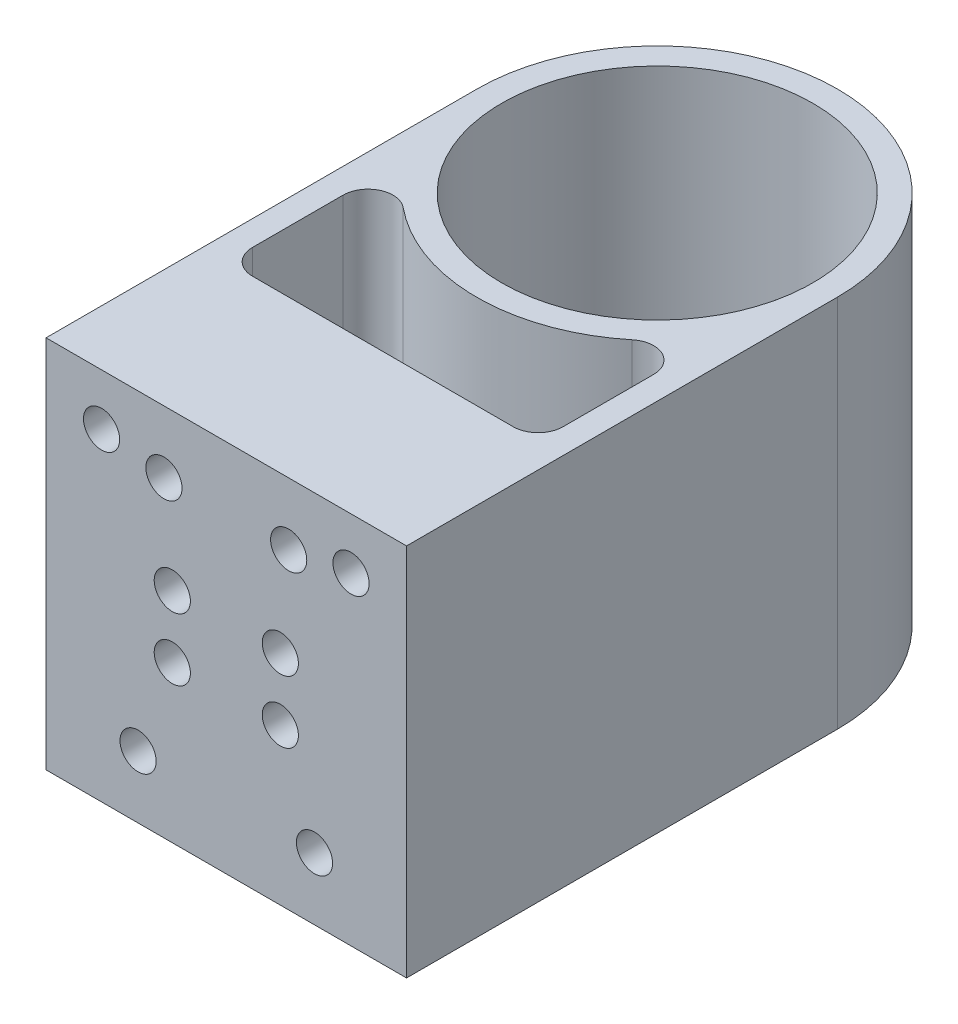
SolidWorks part; units mm, degrees
ref_plane "Alzado" through (0, 0, 0) normal (0, 0, 1) x (1, 0, 0)
ref_plane "Planta" through (0, 0, 0) normal (0, 1, 0) x (1, 0, 0)
ref_plane "Vista lateral" through (0, 0, 0) normal (1, 0, 0) x (0, 0, -1)
sketch "Croquis1" plane through (0, 0, 0) normal (0, 1, 0) x (1, 0, 0)
  circle A0 centre (0, 0) radius 14.45
  dimension "D1" = 28.9
extrude "Saliente-Extruir1" add sketch "Croquis1" along normal blind 30
sketch "Croquis3" plane through (0, 0, 0) normal (0, 1, 0) x (1, 0, 0)
  line L0 (-14.45, 0) -> (14.45, 0)
  line L1 (-14.45, 0) -> (-14.45, -18.45)
  line L2 (14.45, 0) -> (14.45, -18.45)
  line L3 (-14.45, -18.45) -> (14.45, -18.45)
  circle A0 centre (0, 0) radius 14.45 construction
  dimension "D1" = 18.45
extrude "Saliente-Extruir2" add sketch "Croquis3" along normal blind 30
sketch "Croquis4" plane through (0, 30, 0) normal (0, 1, 0) x (1, 0, 0)
  line L0 (-14.45, -18.45) -> (14.45, -18.45)
  line L1 (-14.45, -18.45) -> (-14.45, -0.086)
  line L2 (14.45, -18.45) -> (14.45, -0.086)
  line L3 (-14.45, -0.086) -> (-14.4497, -0.086)
  line L4 (-14.45, -0.086) -> (14.45, -18.45) construction
  line L5 (14.45, -0.086) -> (-14.45, -18.45) construction
  line L6 (14.4497, -0.086) -> (14.45, -0.086)
  line L11 (-10.9106, -15.5619) -> (12.45, -2.086) construction
  line L12 (-13.0398, -2.6759) -> (12.45, -15.5619) construction
  circle A0 centre (0, 0) radius 12.475
  arc A3 (14.4497, -0.0862) -> (14.4497, -0.086) centre (0, 0) ccw
  arc A4 (-14.4497, -0.086) -> (-14.4497, -0.0862) centre (0, 0) ccw
  point P4 (0, -9.268)
  dimension "D1" = 24.95
extrude "Cortar-Extruir2" cut sketch "Croquis4" against normal blind 28 contours A0 region at (0, 30, 0)
sketch "Croquis6" plane through (0, 2, 0) normal (0, 1, 0) x (1, 0, 0)
  line L0 (-12.475, 0) -> (12.475, 0) construction
  line L1 (0, 12.475) -> (0, -12.475) construction
  circle A0 centre (0, 0) radius 12.475 construction
  circle A1 centre (0, 0) radius 12.475 construction
  circle A2 centre (8.65, 0) radius 1.5
  circle A3 centre (-8.65, 0) radius 1.5
  dimension "D1" = 8.65
  dimension "D2" = 3
extrude "Cortar-Extruir4" cut sketch "Croquis6" against normal blind 28
sketch "Croquis7" plane through (0, 0, 18.45) normal (0, 0, 1) x (1, 0, 0)
  line L0 (0, 30) -> (0, 0) construction
  line L1 (-14.45, 30) -> (14.45, 30) construction
  line L2 (-14.45, 20) -> (14.45, 20) construction
  line L3 (-14.45, 30) -> (-14.45, 0) construction
  line L4 (14.45, 30) -> (14.45, 0) construction
  line L5 (-10, 30) -> (-10, 0) construction
  line L6 (-14.45, 0) -> (14.45, 0) construction
  line L7 (10, 30) -> (10, 0) construction
  line L8 (-10, 30) -> (0, 20) construction
  line L9 (0, 20) -> (10, 30) construction
  line L10 (10, 20) -> (0, 30) construction
  line L11 (0, 30) -> (-10, 20) construction
  line L12 (-14.45, 15) -> (10, 15) construction
  line L13 (-16.7125, 24.649) -> (16.7125, 5.351) construction
  line L14 (0, 15) -> (-2.302, 11.0128) construction
  circle A0 centre (-5, 25) radius 1.45
  circle A1 centre (5, 25) radius 1.45
  circle A6 centre (-7.0711, 5) radius 1.45
  circle A7 centre (7.0711, 5) radius 1.45
  circle A9 centre (-4.3301, 17.5) radius 1.45
  circle A10 centre (4.3301, 12.5) radius 1.45
  circle A11 centre (-10, 25.88) radius 1.45
  circle A12 centre (10, 25.88) radius 1.45
  circle A13 centre (-4.3301, 12.5) radius 1.45
  circle A14 centre (4.3301, 17.5) radius 1.45
  point P35 (0, 15)
  dimension "D3" = 2.9
  dimension "D4" = 2.9
  dimension "D6" = 2.9
  dimension "D8" = 90
  dimension "D10" = 2.9
  dimension "D12" = 2.9
  dimension "D13" = 20
  dimension "D14" = 10.88
  dimension "D1" = 10
  dimension "D2" = 10
  dimension "D5" = 20
  dimension "D7" = 7.0711
  dimension "D9" = 30
  dimension "D11" = 5
extrude "Cortar-Extruir5" cut sketch "Croquis7" against normal blind 3
sketch "Croquis8" plane through (0, 0, 0) normal (0, -1, 0) x (1, 0, 0)
  circle A0 centre (0, 0) radius 3.65
  dimension "D1" = 7.3
extrude "Cortar-Extruir6" cut sketch "Croquis8" against normal blind 2
sketch "Croquis9" plane through (0, 0, 18.45) normal (0, 0, 1) x (1, 0, 0)
  line L4 (-14.45, 0) -> (14.45, 0)
  line L5 (14.45, 0) -> (14.45, 30)
  line L6 (14.45, 30) -> (-14.45, 30)
  line L7 (-14.45, 30) -> (-14.45, 0)
  line L8 (-14.45, 0) -> (14.45, 0)
  line L9 (14.45, 0) -> (14.45, 30)
  line L10 (14.45, 30) -> (-14.45, 30)
  line L11 (-14.45, 30) -> (-14.45, 0)
  circle A0 centre (5, 25) radius 1.45 construction
  circle A1 centre (-5, 25) radius 1.45 construction
  circle A2 centre (-4.3301, 12.5) radius 1.45
  circle A3 centre (4.3301, 17.5) radius 1.45
  circle A10 centre (-5, 25) radius 1.45
  circle A11 centre (5, 25) radius 1.45
  circle A12 centre (-7.0711, 5) radius 1.45
  circle A13 centre (7.0711, 5) radius 1.45
  circle A14 centre (-4.3301, 17.5) radius 1.45
  circle A15 centre (4.3301, 12.5) radius 1.45
  circle A16 centre (-10, 25.88) radius 1.45
  circle A17 centre (10, 25.88) radius 1.45
  dimension "D1" = 0
extrude "Saliente-Extruir4" add sketch "Croquis9" along normal blind 16.1
sketch "Croquis10" plane through (0, 30, 0) normal (0, 1, 0) x (1, 0, 0)
  line L3 (-10.45, -22) -> (10.45, -22)
  line L6 (-12.45, 0) -> (-12.45, -32.55)
  line L7 (-12.45, -32.55) -> (12.45, -32.55)
  line L8 (12.45, -32.55) -> (12.45, 0)
  line L9 (-12.45, -12.7367) -> (-12.45, -20)
  line L11 (12.45, -20) -> (12.45, -12.7367)
  arc A2 (12.45, 0) -> (-12.45, 0) centre (0, 0) ccw
  arc A4 (-10.45, -22) -> (-12.45, -20) centre (-10.45, -20) cw
  circle A5 centre (0, 0) radius 14.475
  arc A6 (-9.1814, -11.1905) -> (9.1814, -11.1905) centre (0, 0) ccw
  arc A7 (10.45, -22) -> (12.45, -20) centre (10.45, -20) ccw
  arc A8 (9.1814, -11.1905) -> (12.45, -12.7367) centre (10.45, -12.7367) cw
  arc A9 (-9.1814, -11.1905) -> (-12.45, -12.7367) centre (-10.45, -12.7367) ccw
  dimension "D3" = 22
  dimension "D4" = 2
  dimension "D1" = 2
  dimension "D2" = 2
extrude "Cortar-Extruir7" cut sketch "Croquis10" against normal through all
